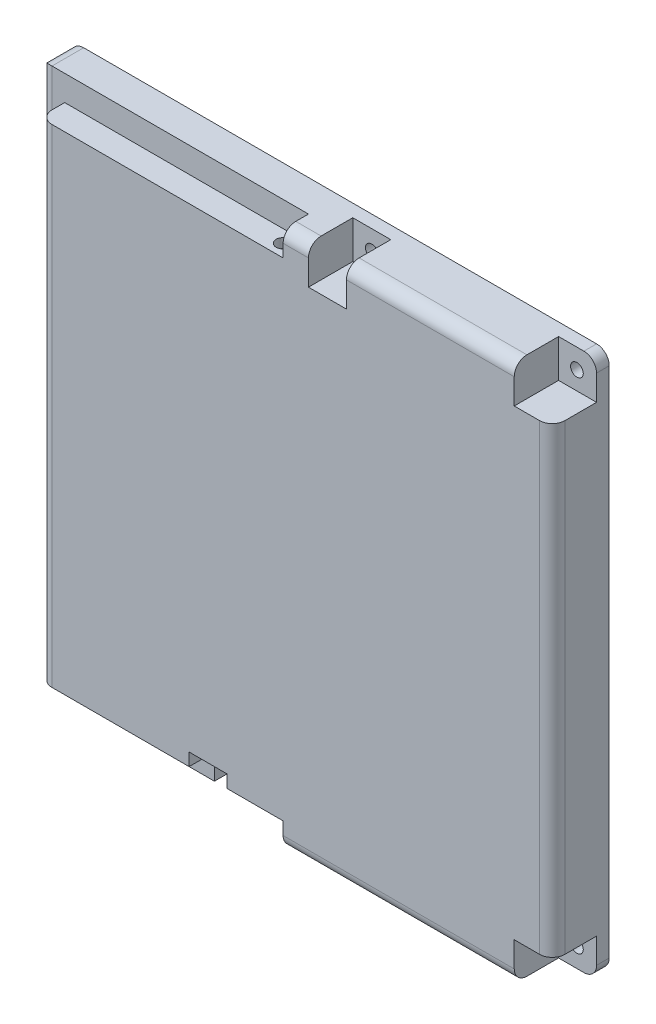
SolidWorks part; units mm, degrees
ref_plane "前视基准面" through (0, 0, 0) normal (0, 0, 1) x (1, 0, 0)
ref_plane "上视基准面" through (0, 0, 0) normal (0, 1, 0) x (1, 0, 0)
ref_plane "右视基准面" through (0, 0, 0) normal (1, 0, 0) x (0, 0, -1)
sketch "草图1" plane through (0, 0, 0) normal (0, 0, 1) x (1, 0, 0)
  line L2 (70.4448, 16.0581) -> (70.4448, -68.9419)
  line L3 (70.4448, -68.9419) -> (155.4453, -68.9419)
  line L4 (70.4448, 16.0581) -> (155.4448, 16.0581)
  line L5 (155.4448, 16.0581) -> (155.4453, 16.0581)
  line L8 (155.4453, 16.0581) -> (155.4453, -68.9419)
  dimension "D1" = 85
  dimension "D2" = 85
extrude "凸台-拉伸1" add sketch "草图1" along normal blind 9
sketch "草图4" plane through (0, 0, 9) normal (0, 0, 1) x (1, 0, 0)
  line L1 (112.9451, 16.0581) -> (70.4448, 16.0581)
  line L6 (70.4448, 16.0581) -> (70.4448, -68.9419)
  line L10 (112.9451, -68.9419) -> (112.9451, 16.0581) construction
  line L11 (70.4448, -68.9419) -> (155.4453, -68.9419) construction
  line L13 (70.4448, -68.9419) -> (112.9451, -68.9419)
  line L14 (112.9451, -68.9419) -> (112.9451, -64.9419)
  line L15 (112.9451, -64.9419) -> (74.4448, -64.9419)
  line L16 (74.4448, -64.9419) -> (74.4448, 12.0581)
  line L17 (74.4448, 12.0581) -> (112.9451, 12.0581)
  line L18 (112.9451, 12.0581) -> (112.9451, 16.0581)
  dimension "D1" = 4
  dimension "D2" = 4
  dimension "D3" = 4
extrude "支架切除-拉伸2" cut sketch "草图4" against normal blind 4
sketch "草图7" plane through (0, 0, 9) normal (0, 0, 1) x (1, 0, 0)
  line L0 (155.4453, -26.4419) -> (112.9448, -26.4419) construction
  line L1 (155.4453, 16.0581) -> (149.4453, 16.0581)
  line L2 (155.4453, 16.0581) -> (155.4453, 10.0581)
  line L3 (155.4453, 10.0581) -> (149.4453, 10.0581)
  line L4 (149.4453, 16.0581) -> (149.4453, 10.0581)
  line L5 (155.4453, -68.9419) -> (155.4453, 16.0581) construction
  line L6 (149.4453, -68.9419) -> (149.4453, -62.9419)
  line L7 (155.4453, -62.9419) -> (149.4453, -62.9419)
  line L8 (155.4453, -68.9419) -> (155.4453, -62.9419)
  line L9 (155.4453, -68.9419) -> (149.4453, -68.9419)
  dimension "D1" = 6
  dimension "D2" = 6
extrude "顶螺丝切除-拉伸4" cut sketch "草图7" against normal blind 7
sketch "草图10" plane through (0, 0, 9) normal (0, 0, 1) x (1, 0, 0)
  line L0 (149.4453, 16.0581) -> (112.9451, 16.0581) construction
  line L1 (116.9448, 16.0581) -> (122.9448, 16.0581)
  line L2 (155.4453, -68.9419) -> (155.4453, -62.9419) construction
  line L3 (149.4453, -68.9419) -> (155.4453, -68.9419) construction
  line L4 (155.4453, -62.9419) -> (149.4453, -62.9419) construction
  line L5 (149.4453, -62.9419) -> (149.4453, -68.9419) construction
  line L6 (155.4453, 10.0581) -> (155.4453, 16.0581) construction
  line L7 (155.4453, 16.0581) -> (149.4453, 16.0581) construction
  line L8 (149.4453, 16.0581) -> (149.4453, 10.0581) construction
  line L9 (149.4453, 10.0581) -> (155.4453, 10.0581) construction
  line L10 (155.4453, -68.9419) -> (155.4453, -62.9419) construction
  line L11 (149.4453, -68.9419) -> (155.4453, -68.9419) construction
  line L12 (155.4453, -62.9419) -> (149.4453, -62.9419) construction
  line L13 (149.4453, -62.9419) -> (149.4453, -68.9419) construction
  line L14 (155.4453, 10.0581) -> (155.4453, 16.0581) construction
  line L15 (155.4453, 16.0581) -> (149.4453, 16.0581) construction
  line L16 (149.4453, 16.0581) -> (149.4453, 10.0581) construction
  line L17 (149.4453, 10.0581) -> (155.4453, 10.0581) construction
  line L18 (116.9448, 16.0581) -> (116.9448, 10.0581)
  line L19 (116.9448, 10.0581) -> (122.9448, 10.0581)
  line L20 (122.9448, 16.0581) -> (122.9448, 10.0581)
  line L22 (98.0948, -62.9419) -> (104.0948, -62.9419)
  line L23 (98.0948, -62.9419) -> (98.0948, -68.9419)
  line L24 (98.0948, -68.9419) -> (104.0948, -68.9419)
  line L25 (104.0948, -62.9419) -> (104.0948, -68.9419)
  line L28 (98.0948, -65.9419) -> (104.0948, -65.9419) construction
  line L30 (101.0948, -68.9419) -> (101.0948, -62.9419) construction
  line L31 (70.4448, -68.9419) -> (112.9451, -68.9419) construction
  circle A2 centre (101.0948, -65.8419) radius 0.825 construction
  circle A3 centre (119.9448, 12.9581) radius 0.825 construction
  dimension "D5" = 3
  dimension "D6" = 3
  dimension "D1" = 6
  dimension "D2" = 6
  dimension "D3" = 6
  dimension "D4" = 6
extrude "底螺丝切除-拉伸6" cut sketch "草图10" against normal blind 7
shell "抽壳1" thickness 1.5 removed face at (112.9451, -26.4419, 0)
sketch "草图5" plane through (0, 12.0581, 0) normal (0, 1, 0) x (1, 0, 0)
  line L0 (112.9451, -5) -> (70.4448, -5) construction
  line L2 (112.9451, -5) -> (112.9451, -9) construction
  circle A1 centre (110.9451, -7) radius 1 construction
  circle A2 centre (110.9451, -7) radius 1.1
  dimension "D1" = 2.2
  dimension "D2" = 2
  dimension "D3" = 2
extrude "切除-拉伸3" cut sketch "草图5" against normal blind 4
ref_plane "基准面1" through (0, -26.4419, 0) normal (0, 1, 0) x (1, 0, 0)
mirror "镜向1" about plane through (0, -26.4419, 0) normal (0, 1, 0) of "切除-拉伸3"
sketch "草图6" plane through (0, 0, 9) normal (0, 0, 1) x (1, 0, 0)
  circle A0 centre (152.3448, 12.9581) radius 1
  circle A1 centre (152.3448, -65.8419) radius 1
  dimension "D1" = 2
  dimension "D2" = 2
extrude "顶螺丝切除-拉伸5" cut sketch "草图6" against normal up to next from surface starting at face at (152.4453, 13.0581, 2)
fillet "圆角1" radius 2 10 edges at (131.1952, -68.9419, 9) (114.9449, 16.0581, 9) (70.4448, 16.0581, 2.5) (70.4448, -68.9419, 2.5) (155.4453, -68.9419, 1) (155.4453, 16.0581, 1) (155.4453, -26.4419, 9) (74.4448, -26.4419, 9) (70.4448, -26.4419, 5) (136.1951, 16.0581, 9)
sketch "草图12" plane through (0, 0, 2) normal (0, 0, 1) x (1, 0, 0)
  circle A0 centre (119.9448, 12.9581) radius 1
  circle A3 centre (101.0948, -65.8419) radius 1
  point P4 (101.0948, -65.8419)
  point P7 (119.9448, 12.9581)
  dimension "D1" = 2
extrude "底螺丝切除-拉伸7" cut sketch "草图12" against normal up to next
